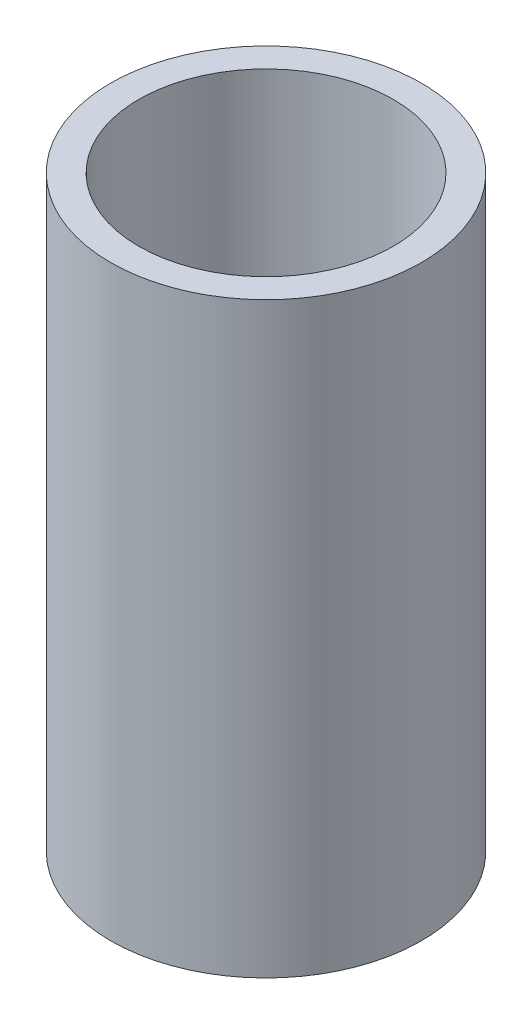
SolidWorks part; units mm, degrees
material "AISI 4130 Steel, annealed at 865C"
ref_plane "Front Plane" through (0, 0, 0) normal (0, 0, 1) x (1, 0, 0)
ref_plane "Top Plane" through (0, 0, 0) normal (0, 1, 0) x (1, 0, 0)
ref_plane "Right Plane" through (0, 0, 0) normal (1, 0, 0) x (0, 0, -1)
sketch "Sketch1" plane through (0, 0, 0) normal (0, 1, 0) x (1, 0, 0)
  circle A0 centre (0, 0) radius 13
  circle A1 centre (0, 0) radius 15.875
  dimension "D1" = 26
  dimension "D2" = 31.75
extrude "Boss-Extrude1" add sketch "Sketch1" along normal blind 60
